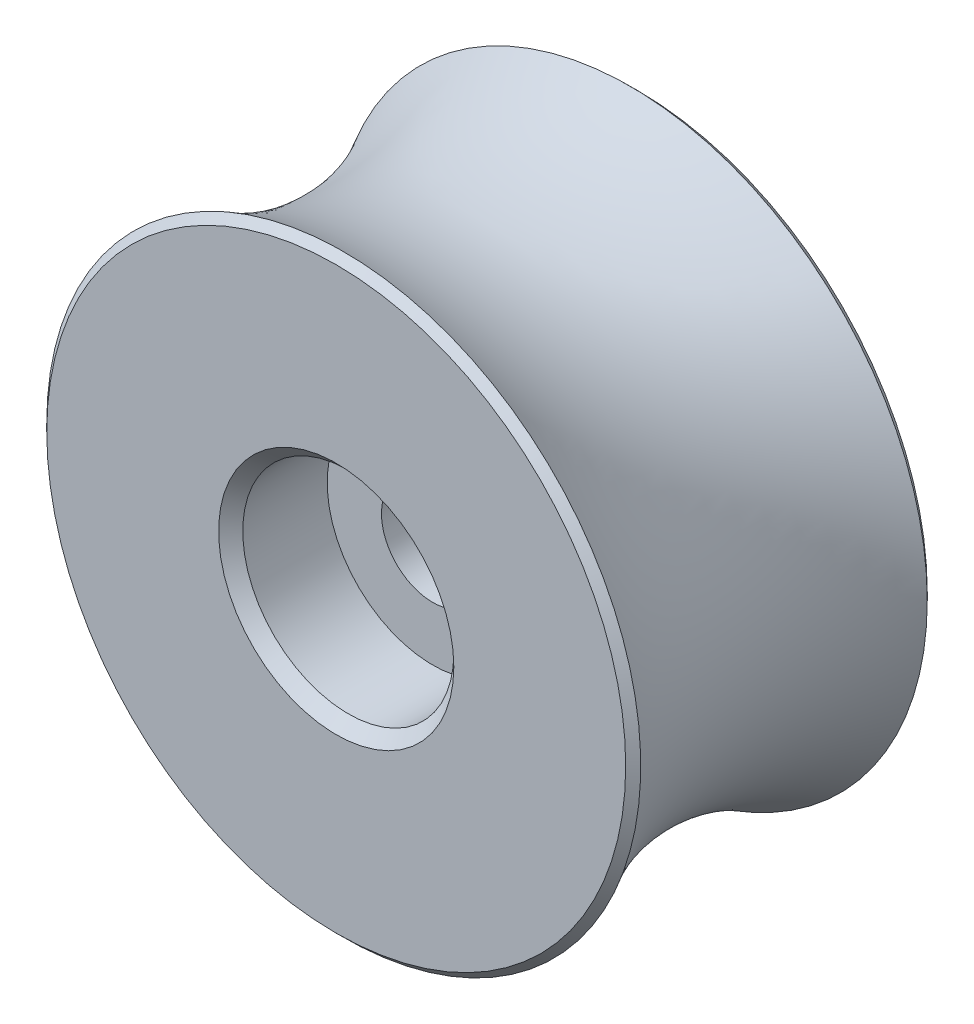
SolidWorks part; units mm, degrees
ref_plane "Front Plane" through (0, 0, 0) normal (0, 0, 1) x (1, 0, 0)
ref_plane "Top Plane" through (0, 0, 0) normal (0, 1, 0) x (1, 0, 0)
ref_plane "Right Plane" through (0, 0, 0) normal (1, 0, 0) x (0, 0, -1)
sketch "Sketch1" plane through (0, 0, 0) normal (0, 0, 1) x (1, 0, 0)
  circle A0 centre (0, 0) radius 10
  dimension "D1" = 20
extrude "Boss-Extrude1" add sketch "Sketch1" along normal blind 10 contours A0
sketch "Sketch2" plane through (0, 0, 10) normal (0, 0, 1) x (1, 0, 0)
  circle A0 centre (0, 0) radius 1.7
  dimension "D1" = 3.4
extrude "Cut-Extrude1" cut sketch "Sketch2" against normal up to next
sketch "Sketch3" plane through (0, 0, 10) normal (0, 0, 1) x (1, 0, 0)
  circle A0 centre (0, 0) radius 3.5
  dimension "D1" = 7
extrude "Cut-Extrude2" cut sketch "Sketch3" against normal blind 3.2
ref_plane "Plane1" through (0, 0, 5) normal (0, 0, 1) x (1, 0, 0)
mirror "Mirror1" about plane through (0, 0, 5) normal (0, 0, 1) of "Cut-Extrude2"
sketch "Sketch4" plane through (0, 0, 0) normal (0, 1, 0) x (1, 0, 0)
  line L0 (10, 0) -> (-10, 0) construction
  line L1 (-10, -10) -> (10, -10) construction
  line L2 (10, 0) -> (-10, 0) construction
  line L3 (-10, -10) -> (10, -10) construction
  line L4 (10, -10) -> (10, 0)
  line L5 (10, -5) -> (18, -5) construction
  circle A0 centre (18, -5) radius 9.434 construction
  arc A1 (10, -10) -> (10, 0) centre (18, -5) cw
  point P9 (0, 0)
  dimension "D1" = 8
ref_axis "Axis1" through (0, 0, 3.2) along (0, 0, 1)
revolve "Cut-Revolve1" cut sketch "Sketch4" angle 360 about axis through (0, 0, 3.2) along (0, 0, 1)
chamfer "Chamfer1" distance 0.4 angle 45 3 edges at (-10, 0, 10) (3.5, 0, 10) (3.5, 0, 0) first distance on face at (3.5, 0, 10) first distance on face at (3.5, 0, 3.2)
chamfer "Chamfer2" distance 0.4 angle 45 1 edges at (-10, 0, 0) first distance on face at (3.9, 0, 0)
